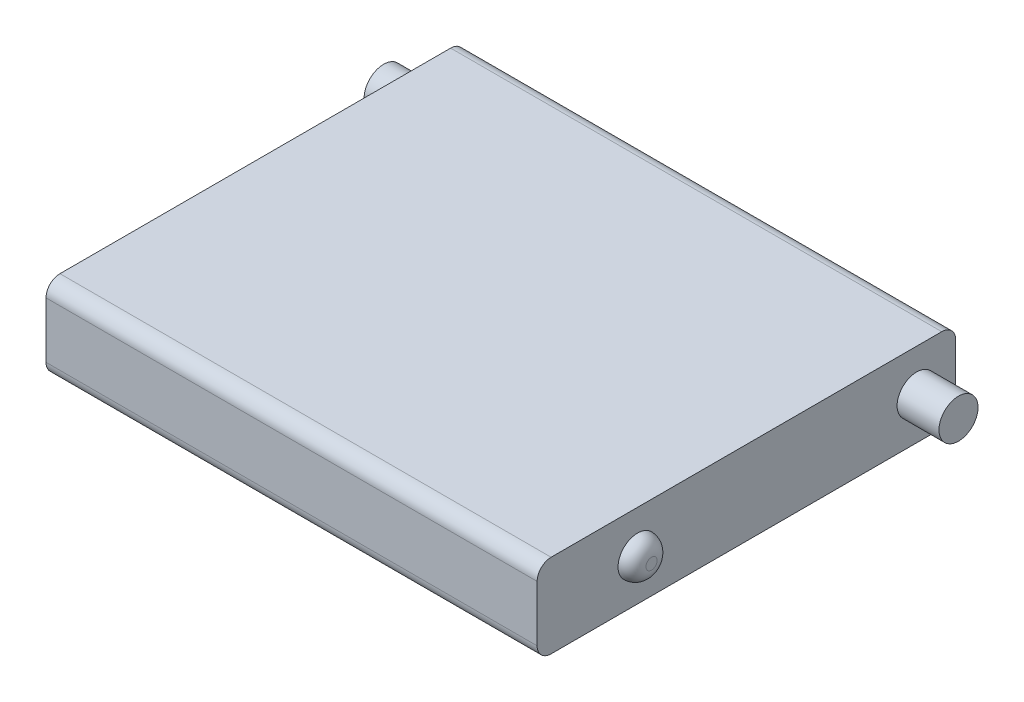
SolidWorks part; units mm, degrees
material "PP Copolymer"
ref_plane "Front Plane" through (0, 0, 0) normal (0, 0, 1) x (1, 0, 0)
ref_plane "Top Plane" through (0, 0, 0) normal (0, 1, 0) x (1, 0, 0)
ref_plane "Right Plane" through (0, 0, 0) normal (1, 0, 0) x (0, 0, -1)
sketch "Sketch1" plane through (0, 0, 0) normal (0, 1, 0) x (1, 0, 0)
  line L1 (-8.8, 7.5) -> (8.8, 7.5)
  line L2 (-8.8, 7.5) -> (-8.8, -7.5)
  line L3 (-8.8, -7.5) -> (8.8, -7.5)
  line L4 (8.8, 7.5) -> (8.8, -7.5)
  line L5 (-8.8, 7.5) -> (8.8, -7.5) construction
  line L6 (-8.8, -7.5) -> (8.8, 7.5) construction
  point P0 (0, 0)
  dimension "D1" = 17.6
  dimension "D2" = 15
extrude "Boss-Extrude1" add sketch "Sketch1" along normal mid plane 3
sketch "Sketch2" plane through (0, -1.5, 0) normal (0, -1, 0) x (1, 0, 0)
  line L0 (-8.8, 7.5) -> (8.8, 7.5) construction
  line L1 (-7.4, 5) -> (7.4, 5)
  line L2 (-7.4, 5) -> (-7.4, -5)
  line L3 (-7.4, -5) -> (7.4, -5)
  line L4 (7.4, 5) -> (7.4, -5)
  line L5 (-7.4, 5) -> (7.4, -5) construction
  line L6 (-7.4, -5) -> (7.4, 5) construction
  line L7 (8.8, 7.5) -> (8.8, -7.5) construction
  point P0 (0, 0)
  dimension "D1" = 2.5
  dimension "D2" = 1.4
extrude "Cut-Extrude1" cut sketch "Sketch2" against normal blind 1.4
sketch "Sketch3" plane through (-8.8, 0, 0) normal (-1, 0, 0) x (0, 0, 1)
  line L0 (-7.5, 0) -> (-6.1, 0) construction
  line L1 (-7.5, 1.5) -> (-7.5, -1.5) construction
  circle A0 centre (-6.1, 0) radius 0.7
  dimension "D1" = 1.4
  dimension "D2" = 1.4
extrude "Boss-Extrude2" add sketch "Sketch3" along normal blind 1.5
sketch "Sketch4" plane through (-8.8, 0, 0) normal (-1, 0, 0) x (0, 0, 1)
  line L0 (-6.1, 0) -> (3.9, 0) construction
  circle A0 centre (3.9, 0) radius 0.7
  circle A1 centre (-6.1, 0) radius 0.7 construction
  dimension "D1" = 10
extrude "Boss-Extrude3" add sketch "Sketch4" along normal blind 0.5
fillet "Fillet2" radius 0.5 1 edges at (-9.3, 0, 4.6)
mirror "Mirror1" about plane through (0, 0, 0) normal (1, 0, 0) of "Boss-Extrude3", "Fillet2", "Boss-Extrude2"
fillet "Fillet1" radius 0.5 4 edges at (0, -1.5, -7.5) (0, 1.5, -7.5) (0, -1.5, 7.5) (0, 1.5, 7.5)
